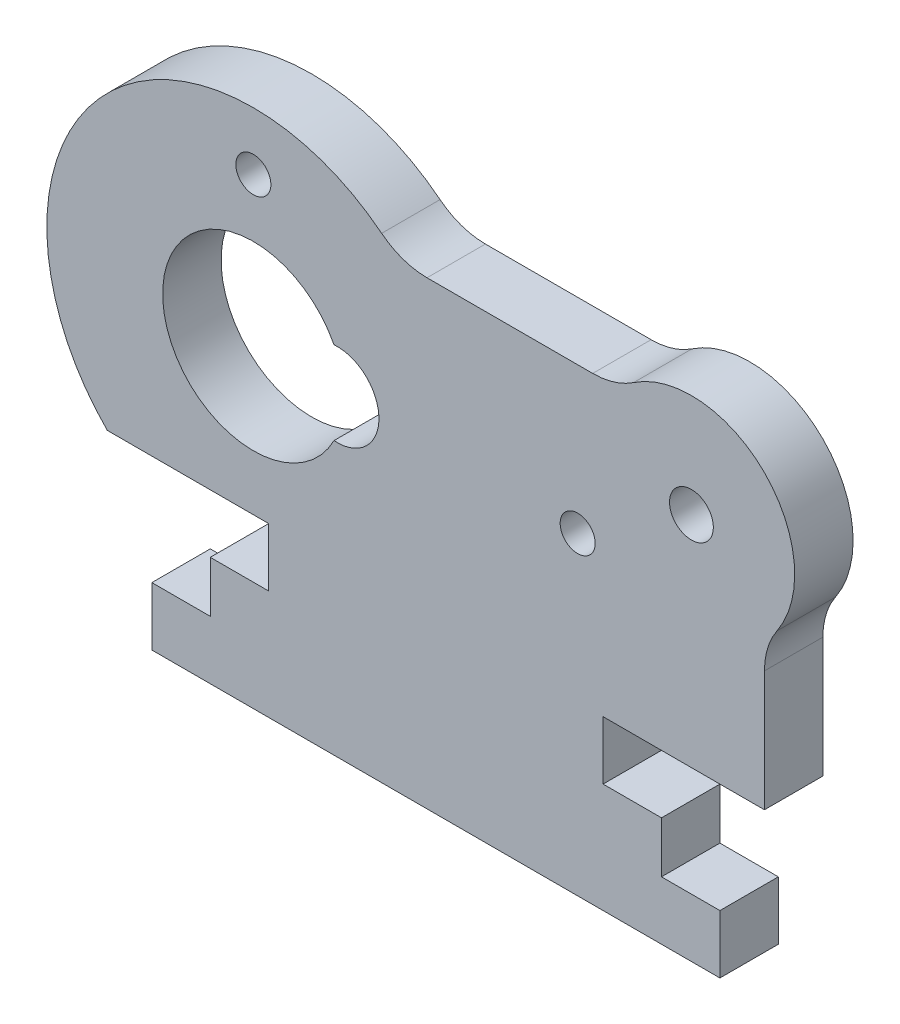
SolidWorks part; units mm, degrees
ref_plane "Front Plane" through (0, 0, 0) normal (0, 0, 1) x (1, 0, 0)
ref_plane "Top Plane" through (0, 0, 0) normal (0, 1, 0) x (1, 0, 0)
ref_plane "Right Plane" through (0, 0, 0) normal (1, 0, 0) x (0, 0, -1)
sketch "Sketch2" plane through (0, 0, 0) normal (0, 0, 1) x (1, 0, 0)
  line L0 (0, 0) -> (0, 4)
  line L1 (0, 4) -> (4, 4)
  line L2 (4, 4) -> (4, 7.5)
  line L3 (4, 7.5) -> (8, 7.5)
  line L4 (8, 7.5) -> (8, 11.5)
  line L5 (8, 11.5) -> (-3.05, 11.5)
  line L6 (-3.05, 31.5) -> (41.95, 31.5)
  line L7 (41.95, 31.5) -> (41.95, 11.5)
  line L8 (41.95, 11.5) -> (30.9, 11.5)
  line L9 (30.9, 11.5) -> (30.9, 7.5)
  line L10 (30.9, 7.5) -> (34.9, 7.5)
  line L11 (34.9, 7.5) -> (34.9, 4)
  line L12 (34.9, 4) -> (38.9, 4)
  line L13 (38.9, 4) -> (38.9, 0)
  line L14 (38.9, 0) -> (0, 0)
  line L15 (-3.05, 31.5) -> (-3.05, 11.5)
  line L16 (6.95, 27.71) -> (6.95, 35.6421) construction
  line L17 (0.74, 27.71) -> (23.16, 27.71)
  line L18 (0.74, 27.71) -> (0.74, 15.29)
  line L19 (0.74, 15.29) -> (23.16, 15.29)
  line L20 (23.16, 27.71) -> (23.16, 15.29)
  circle A1 centre (6.95, 21.5) radius 14.1421
  circle A2 centre (36.95, 26.5) radius 1.5
  circle A4 centre (36.95, 26.5) radius 7.0711
  circle A5 centre (6.95, 21.5) radius 6.21
  circle A6 centre (6.95, 21.5) radius 1.5
  arc A7 (12.4721, 24.3409) -> (12.4721, 18.6591) centre (12.7, 21.5) cw
  circle A8 centre (6.95, 31.6761) radius 1.2
  circle A9 centre (29.16, 21.5) radius 1.2
  point P2 (0.74, 21.5)
  point P3 (19.45, 0)
  point P10 (19.45, 31.5)
  point P24 (-3.05, 21.5)
  point P38 (6.95, 31.6761)
  dimension "D5" = 22.42
  dimension "D10" = 30
  dimension "D13" = 3
  dimension "D15" = 3
  dimension "D7" = 10
  dimension "D9" = 5.75
  dimension "D16" = 2.85
  dimension "D18" = 2.4
  dimension "D1" = 4
  dimension "D2" = 22.9
  dimension "D3" = 4
  dimension "D4" = 4
  dimension "D6" = 12.42
  dimension "D8" = 10
  dimension "D11" = 5
  dimension "D12" = 5
  dimension "D14" = 3.5
  dimension "D17" = 6
extrude "Boss-Extrude1" add sketch "Sketch2" along normal blind 4 contours L15 A1 | L17 A1 L6 L15 L5 L4 L19 L18 | L6 A1 | L6 A4 L7 A2 | L6 A4 | L7 A4 | A4 L6 A1 L17 L20 L19 L4 L3 L2 L1 L0 L14 L13 L12 L11 L10 L9 L8 L7 | A5 L17 L18 | A5 A7 L19 A1 L17 | A1 L19 L20 L17 | A5 L18 L19 | A8 L16 A1 L6 | L16 L17 A1 L6 A8 region at (24.3098, 11.4692, 0) region at (6.475, 7.4669, 0) region at (-4.7296, 21.5, 0) region at (21.8562, 21.5, 0) region at (16.3715, 21.5, 0) region at (2.9507, 33.2332, 0) region at (2.1271, 16.6771, 0) region at (10.9493, 33.2332, 0) region at (2.1271, 26.3229, 0) region at (12.8459, 29.4982, 0) region at (32.0707, 21.6207, 0) region at (42.7898, 26.5, 0) region at (36.95, 32.3398, 0)
fillet "Fillet1" radius 5 3 edges at (41.95, 21.5, 2) (31.95, 31.5, 2) (16.95, 31.5, 2)
